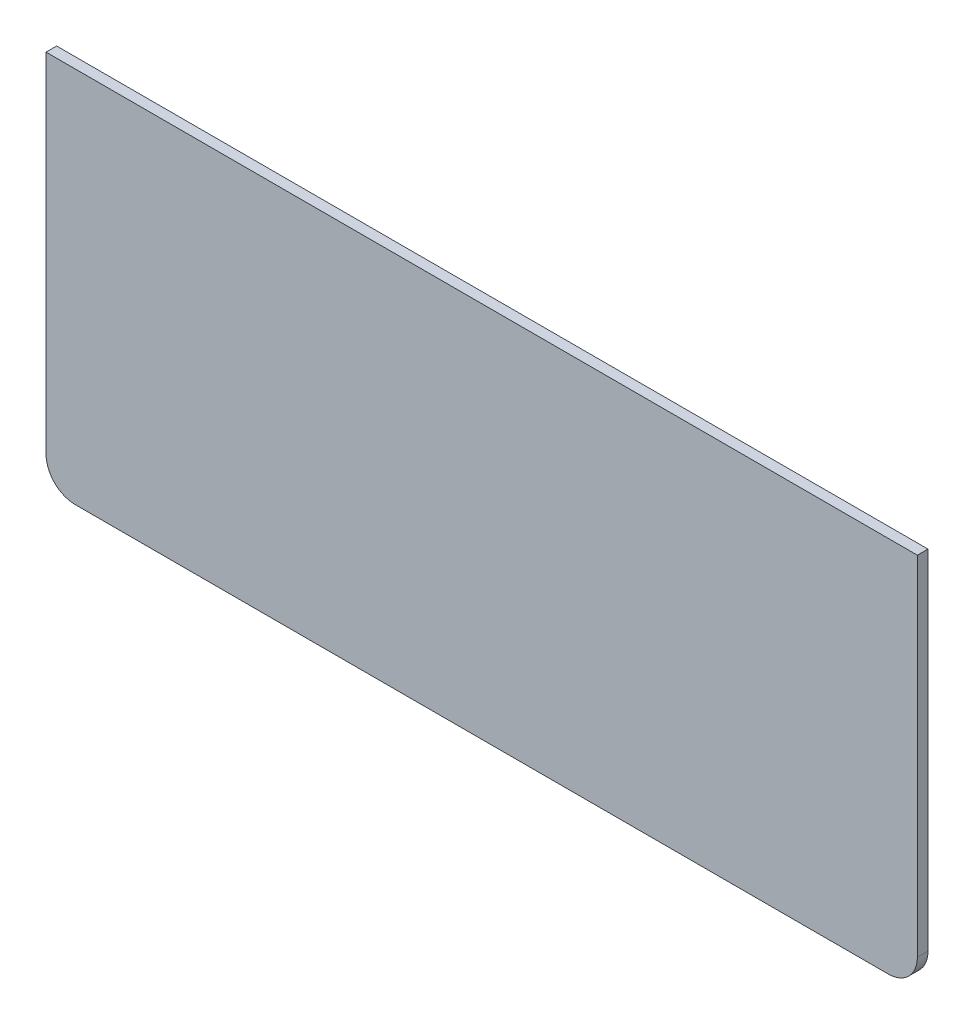
SolidWorks part; units mm, degrees
material "5052-H32"
ref_plane "Front Plane" through (0, 0, 0) normal (0, 0, 1) x (1, 0, 0)
ref_plane "Top Plane" through (0, 0, 0) normal (0, 1, 0) x (1, 0, 0)
ref_plane "Right Plane" through (0, 0, 0) normal (1, 0, 0) x (0, 0, -1)
sketch "Sketch2" plane through (0, 0, 0) normal (0, 0, 1) x (1, 0, 0)
  line L0 (-53.5866, 40.5355) -> (207.7634, 40.5355)
  line L1 (207.7634, 40.5355) -> (207.7634, -72.6395)
  line L2 (207.7634, -72.6395) -> (-53.5866, -72.6395)
  line L3 (-53.5866, -72.6395) -> (-53.5866, 40.5355)
  dimension "D1" = 113.175
  dimension "D2" = 261.35
extrude "Boss-Extrude1" add sketch "Sketch2" along normal blind 3.175
fillet "Fillet1" radius 8.7312 2 edges at (-53.5866, -72.6395, 1.5875) (207.7634, -72.6395, 1.5875)
equation "\"L\"= 410mm"
equation "\"W\"= 255mm"
equation "\"H\"= 110mm"
equation "\"Compartment Width\"= 80"
equation "\"T\"= 4.7625 * 2 / 3mm"
equation "\"Inside Fillet Radius\"= 5.55625mm"
equation "\"D1@Fillet1\"=\"Inside Fillet Radius\"+\"T\""
equation "\"D1@Sketch2\"=\"T\"+\"H\""
equation "\"D2@Sketch2\"=2*\"T\"+\"W\""
equation "\"D1@Boss-Extrude1\"=\"T\""
equation "\"Offset\"= 13mm"
equation "\"Hole\"=15mm"
equation "\"Wheel to Wall\"= 43"
